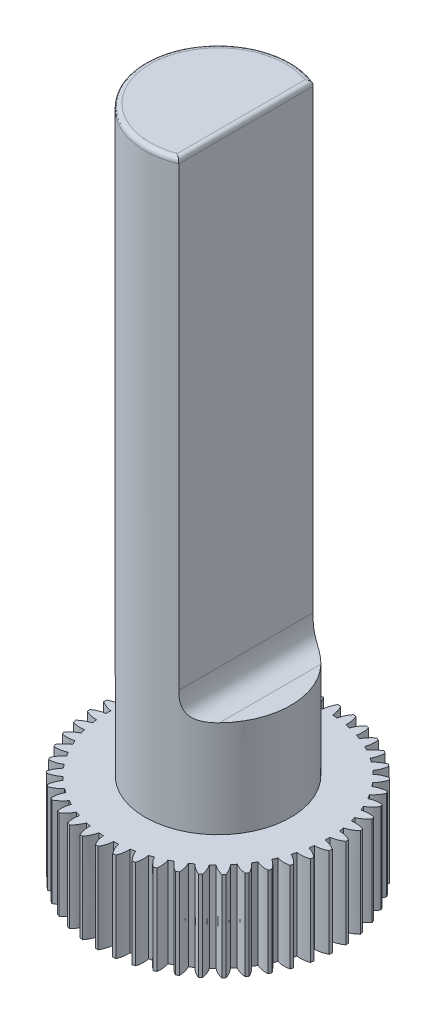
SolidWorks part; units mm, degrees
ref_plane "Front Plane" through (0, 0, 0) normal (0, 0, 1) x (1, 0, 0)
ref_plane "Top Plane" through (0, 0, 0) normal (0, 1, 0) x (1, 0, 0)
ref_plane "Right Plane" through (0, 0, 0) normal (1, 0, 0) x (0, 0, -1)
sketch "Sketch1" plane through (0, 0, 0) normal (0, 1, 0) x (1, 0, 0)
  circle A0 centre (0, 0) radius 1.5
  dimension "D1" = 3
extrude "Boss-Extrude1" add sketch "Sketch1" along normal blind 12
sketch "Sketch2" plane through (0, 12, 0) normal (0, 1, 0) x (1, 0, 0)
  line L0 (0.576, 1.385) -> (0.576, -1.385)
  circle A0 centre (0, 0) radius 1.5 construction
  arc A1 (0.576, -1.385) -> (0.576, 1.385) centre (0, 0) ccw
  dimension "D1" = 2.77
extrude "Cut-Extrude1" cut sketch "Sketch2" against normal blind 10
fillet "Fillet2" radius 0.5 1 edges at (0.576, 2, 0) curvature continuous yes
fillet "Fillet3" radius 0.1 2 edges at (-1.5, 12, 0) (0.576, 12, 0) curvature continuous yes
sketch "Sketch3" plane through (0, 0, 0) normal (0, -1, 0) x (1, 0, 0)
  circle A0 centre (0, 0) radius 2.26
  dimension "D1" = 4.52
extrude "Boss-Extrude2" add sketch "Sketch3" along normal blind 1.85
sketch "Sketch4" plane through (0, -1.85, 0) normal (0, -1, 0) x (1, 0, 0)
  line L0 (0, 3.4014) -> (0, -2.7756) construction
  line L1 (-0.03, 2.5) -> (0.03, 2.5)
  line L2 (0.3107, 2.4808) -> (0.3701, 2.4726)
  line L3 (0.105, 2.7453) -> (0.105, 2.2073) construction
  line L4 (0.6456, 2.4154) -> (0.7034, 2.3992)
  line L5 (0.9685, 2.305) -> (1.0235, 2.2811)
  line L6 (1.2733, 2.1516) -> (1.3246, 2.1205)
  line L7 (1.5544, 1.9582) -> (1.601, 1.9203)
  line L8 (1.8066, 1.7283) -> (1.8476, 1.6845)
  line L9 (2.0251, 1.4662) -> (2.0597, 1.4172)
  line L10 (2.2059, 1.1768) -> (2.2335, 1.1235)
  line L11 (2.3456, 0.8655) -> (2.3657, 0.8089)
  line L12 (2.4416, 0.538) -> (2.4538, 0.4793)
  line L13 (2.4921, 0.2005) -> (2.4962, 0.1407)
  line L14 (2.4962, -0.1407) -> (2.4921, -0.2005)
  line L15 (2.4538, -0.4793) -> (2.4416, -0.538)
  line L16 (2.3657, -0.8089) -> (2.3456, -0.8655)
  line L17 (2.2335, -1.1235) -> (2.2059, -1.1768)
  line L18 (2.0597, -1.4172) -> (2.0251, -1.4662)
  line L19 (1.8476, -1.6845) -> (1.8066, -1.7283)
  line L20 (1.601, -1.9203) -> (1.5544, -1.9582)
  line L21 (1.3246, -2.1205) -> (1.2733, -2.1516)
  line L22 (1.0235, -2.2811) -> (0.9685, -2.305)
  line L23 (0.7034, -2.3992) -> (0.6456, -2.4154)
  line L24 (0.3701, -2.4726) -> (0.3107, -2.4808)
  line L25 (0.03, -2.5) -> (-0.03, -2.5)
  line L26 (-0.3107, -2.4808) -> (-0.3701, -2.4726)
  line L27 (-0.6456, -2.4154) -> (-0.7034, -2.3992)
  line L28 (-0.9685, -2.305) -> (-1.0235, -2.2811)
  line L29 (-1.2733, -2.1516) -> (-1.3246, -2.1205)
  line L30 (-1.5544, -1.9582) -> (-1.601, -1.9203)
  line L31 (-1.8066, -1.7283) -> (-1.8476, -1.6845)
  line L32 (-2.0251, -1.4662) -> (-2.0597, -1.4172)
  line L33 (-2.2059, -1.1768) -> (-2.2335, -1.1235)
  line L34 (-2.3456, -0.8655) -> (-2.3657, -0.8089)
  line L35 (-2.4416, -0.538) -> (-2.4538, -0.4793)
  line L36 (-2.4921, -0.2005) -> (-2.4962, -0.1407)
  line L37 (-2.4962, 0.1407) -> (-2.4921, 0.2005)
  line L38 (-2.4538, 0.4793) -> (-2.4416, 0.538)
  line L39 (-2.3657, 0.8089) -> (-2.3456, 0.8655)
  line L40 (-2.2335, 1.1235) -> (-2.2059, 1.1768)
  line L41 (-2.0597, 1.4172) -> (-2.0251, 1.4662)
  line L42 (-1.8476, 1.6845) -> (-1.8066, 1.7283)
  line L43 (-1.601, 1.9203) -> (-1.5544, 1.9582)
  line L44 (-1.3246, 2.1205) -> (-1.2733, 2.1516)
  line L45 (-1.0235, 2.2811) -> (-0.9685, 2.305)
  line L46 (-0.7034, 2.3992) -> (-0.6456, 2.4154)
  line L47 (-0.3701, 2.4726) -> (-0.3107, 2.4808)
  circle A0 centre (0, 0) radius 2.26 construction
  spline S0 degree 2 poles (0.03, 2.5) (0.0998, 2.3793) (0.105, 2.2491) knots 0 0 0 0.862406 0.862406 0.862406
  spline S1 degree 1 poles (0, 2.26) (0.105, 2.2491) knots 0 0 1 1
  spline S2 degree 1 poles (0, 2.26) (-0.105, 2.2491) knots 0 0 1 1
  spline S3 degree 2 poles (-0.03, 2.5) (-0.0998, 2.3793) (-0.105, 2.2491) knots 0 0 0 0.862406 0.862406 0.862406
  spline S4 degree 2 poles (0.3107, 2.4808) (0.2251, 2.3707) (0.2022, 2.2424) knots 0 0 0 0.862406 0.862406 0.862406
  spline S5 degree 1 poles (0.3077, 2.239) (0.2022, 2.2424) knots 0 0 1 1
  spline S6 degree 1 poles (0.3077, 2.239) (0.4103, 2.2138) knots 0 0 1 1
  spline S7 degree 2 poles (0.3701, 2.4726) (0.4229, 2.3435) (0.4103, 2.2138) knots 0 0 0 0.862406 0.862406 0.862406
  spline S8 degree 2 poles (0.6456, 2.4154) (0.5458, 2.318) (0.5057, 2.194) knots 0 0 0 0.862406 0.862406 0.862406
  spline S9 degree 1 poles (0.6097, 2.1762) (0.5057, 2.194) knots 0 0 1 1
  spline S10 degree 1 poles (0.6097, 2.1762) (0.7079, 2.1373) knots 0 0 1 1
  spline S11 degree 2 poles (0.7034, 2.3992) (0.7381, 2.2641) (0.7079, 2.1373) knots 0 0 0 0.862406 0.862406 0.862406
  spline S12 degree 2 poles (0.9685, 2.305) (0.8563, 2.2221) (0.7997, 2.1047) knots 0 0 0 0.862406 0.862406 0.862406
  spline S13 degree 1 poles (0.9004, 2.0729) (0.7997, 2.1047) knots 0 0 1 1
  spline S14 degree 1 poles (0.9004, 2.0729) (0.9923, 2.021) knots 0 0 1 1
  spline S15 degree 2 poles (1.0235, 2.2811) (1.0395, 2.1425) (0.9923, 2.021) knots 0 0 0 0.862406 0.862406 0.862406
  spline S16 degree 2 poles (1.2733, 2.1516) (1.1509, 2.0848) (1.0789, 1.9762) knots 0 0 0 0.862406 0.862406 0.862406
  spline S17 degree 1 poles (1.1743, 1.931) (1.0789, 1.9762) knots 0 0 1 1
  spline S18 degree 1 poles (1.1743, 1.931) (1.2583, 1.8671) knots 0 0 1 1
  spline S19 degree 2 poles (1.3246, 2.1205) (1.3215, 1.981) (1.2583, 1.8671) knots 0 0 0 0.862406 0.862406 0.862406
  spline S20 degree 2 poles (1.5544, 1.9582) (1.4241, 1.9086) (1.3379, 1.8109) knots 0 0 0 0.862406 0.862406 0.862406
  spline S21 degree 1 poles (1.4263, 1.7531) (1.3379, 1.8109) knots 0 0 1 1
  spline S22 degree 1 poles (1.4263, 1.7531) (1.5008, 1.6784) knots 0 0 1 1
  spline S23 degree 2 poles (1.601, 1.9203) (1.579, 1.7826) (1.5008, 1.6784) knots 0 0 0 0.862406 0.862406 0.862406
  spline S24 degree 2 poles (1.8066, 1.7283) (1.6707, 1.6969) (1.572, 1.6118) knots 0 0 0 0.862406 0.862406 0.862406
  spline S25 degree 1 poles (1.6517, 1.5426) (1.572, 1.6118) knots 0 0 1 1
  spline S26 degree 1 poles (1.6517, 1.5426) (1.7154, 1.4584) knots 0 0 1 1
  spline S27 degree 2 poles (1.8476, 1.6845) (1.807, 1.551) (1.7154, 1.4584) knots 0 0 0 0.862406 0.862406 0.862406
  spline S28 degree 2 poles (2.0251, 1.4662) (1.8862, 1.4536) (1.7769, 1.3828) knots 0 0 0 0.862406 0.862406 0.862406
  spline S29 degree 1 poles (1.8464, 1.3033) (1.7769, 1.3828) knots 0 0 1 1
  spline S30 degree 1 poles (1.8464, 1.3033) (1.898, 1.2112) knots 0 0 1 1
  spline S31 degree 2 poles (2.0597, 1.4172) (2.0014, 1.2905) (1.898, 1.2112) knots 0 0 0 0.862406 0.862406 0.862406
  spline S32 degree 2 poles (2.2059, 1.1768) (2.0666, 1.1833) (1.9486, 1.1279) knots 0 0 0 0.862406 0.862406 0.862406
  spline S33 degree 1 poles (2.0066, 1.0397) (1.9486, 1.1279) knots 0 0 1 1
  spline S34 degree 1 poles (2.0066, 1.0397) (2.0452, 0.9415) knots 0 0 1 1
  spline S35 degree 2 poles (2.2335, 1.1235) (2.1584, 1.006) (2.0452, 0.9415) knots 0 0 0 0.862406 0.862406 0.862406
  spline S36 degree 2 poles (2.3456, 0.8655) (2.2085, 0.8908) (2.084, 0.8521) knots 0 0 0 0.862406 0.862406 0.862406
  spline S37 degree 1 poles (2.1295, 0.7568) (2.084, 0.8521) knots 0 0 1 1
  spline S38 degree 1 poles (2.1295, 0.7568) (2.1544, 0.6542) knots 0 0 1 1
  spline S39 degree 2 poles (2.3657, 0.8089) (2.2753, 0.7027) (2.1544, 0.6542) knots 0 0 0 0.862406 0.862406 0.862406
  spline S40 degree 2 poles (2.4416, 0.538) (2.3092, 0.5818) (2.1807, 0.5604) knots 0 0 0 0.862406 0.862406 0.862406
  spline S41 degree 1 poles (2.2127, 0.4598) (2.1807, 0.5604) knots 0 0 1 1
  spline S42 degree 1 poles (2.2127, 0.4598) (2.2234, 0.3548) knots 0 0 1 1
  spline S43 degree 2 poles (2.4538, 0.4793) (2.3498, 0.3863) (2.2234, 0.3548) knots 0 0 0 0.862406 0.862406 0.862406
  spline S44 degree 2 poles (2.4921, 0.2005) (2.3669, 0.262) (2.2367, 0.2582) knots 0 0 0 0.862406 0.862406 0.862406
  spline S45 degree 1 poles (2.2547, 0.1542) (2.2367, 0.2582) knots 0 0 1 1
  spline S46 degree 1 poles (2.2547, 0.1542) (2.251, 0.0487) knots 0 0 1 1
  spline S47 degree 2 poles (2.4962, 0.1407) (2.3805, 0.0628) (2.251, 0.0487) knots 0 0 0 0.862406 0.862406 0.862406
  spline S48 degree 2 poles (2.4962, -0.1407) (2.3805, -0.0628) (2.251, -0.0487) knots 0 0 0 0.862406 0.862406 0.862406
  spline S49 degree 1 poles (2.2547, -0.1542) (2.251, -0.0487) knots 0 0 1 1
  spline S50 degree 1 poles (2.2547, -0.1542) (2.2367, -0.2582) knots 0 0 1 1
  spline S51 degree 2 poles (2.4921, -0.2005) (2.3669, -0.262) (2.2367, -0.2582) knots 0 0 0 0.862406 0.862406 0.862406
  spline S52 degree 2 poles (2.4538, -0.4793) (2.3498, -0.3863) (2.2234, -0.3548) knots 0 0 0 0.862406 0.862406 0.862406
  spline S53 degree 1 poles (2.2127, -0.4598) (2.2234, -0.3548) knots 0 0 1 1
  spline S54 degree 1 poles (2.2127, -0.4598) (2.1807, -0.5604) knots 0 0 1 1
  spline S55 degree 2 poles (2.4416, -0.538) (2.3092, -0.5818) (2.1807, -0.5604) knots 0 0 0 0.862406 0.862406 0.862406
  spline S56 degree 2 poles (2.3657, -0.8089) (2.2753, -0.7027) (2.1544, -0.6542) knots 0 0 0 0.862406 0.862406 0.862406
  spline S57 degree 1 poles (2.1295, -0.7568) (2.1544, -0.6542) knots 0 0 1 1
  spline S58 degree 1 poles (2.1295, -0.7568) (2.084, -0.8521) knots 0 0 1 1
  spline S59 degree 2 poles (2.3456, -0.8655) (2.2085, -0.8908) (2.084, -0.8521) knots 0 0 0 0.862406 0.862406 0.862406
  spline S60 degree 2 poles (2.2335, -1.1235) (2.1584, -1.006) (2.0452, -0.9415) knots 0 0 0 0.862406 0.862406 0.862406
  spline S61 degree 1 poles (2.0066, -1.0397) (2.0452, -0.9415) knots 0 0 1 1
  spline S62 degree 1 poles (2.0066, -1.0397) (1.9486, -1.1279) knots 0 0 1 1
  spline S63 degree 2 poles (2.2059, -1.1768) (2.0666, -1.1833) (1.9486, -1.1279) knots 0 0 0 0.862406 0.862406 0.862406
  spline S64 degree 2 poles (2.0597, -1.4172) (2.0014, -1.2905) (1.898, -1.2112) knots 0 0 0 0.862406 0.862406 0.862406
  spline S65 degree 1 poles (1.8464, -1.3033) (1.898, -1.2112) knots 0 0 1 1
  spline S66 degree 1 poles (1.8464, -1.3033) (1.7769, -1.3828) knots 0 0 1 1
  spline S67 degree 2 poles (2.0251, -1.4662) (1.8862, -1.4536) (1.7769, -1.3828) knots 0 0 0 0.862406 0.862406 0.862406
  spline S68 degree 2 poles (1.8476, -1.6845) (1.807, -1.551) (1.7154, -1.4584) knots 0 0 0 0.862406 0.862406 0.862406
  spline S69 degree 1 poles (1.6517, -1.5426) (1.7154, -1.4584) knots 0 0 1 1
  spline S70 degree 1 poles (1.6517, -1.5426) (1.572, -1.6118) knots 0 0 1 1
  spline S71 degree 2 poles (1.8066, -1.7283) (1.6707, -1.6969) (1.572, -1.6118) knots 0 0 0 0.862406 0.862406 0.862406
  spline S72 degree 2 poles (1.601, -1.9203) (1.579, -1.7826) (1.5008, -1.6784) knots 0 0 0 0.862406 0.862406 0.862406
  spline S73 degree 1 poles (1.4263, -1.7531) (1.5008, -1.6784) knots 0 0 1 1
  spline S74 degree 1 poles (1.4263, -1.7531) (1.3379, -1.8109) knots 0 0 1 1
  spline S75 degree 2 poles (1.5544, -1.9582) (1.4241, -1.9086) (1.3379, -1.8109) knots 0 0 0 0.862406 0.862406 0.862406
  spline S76 degree 2 poles (1.3246, -2.1205) (1.3215, -1.981) (1.2583, -1.8671) knots 0 0 0 0.862406 0.862406 0.862406
  spline S77 degree 1 poles (1.1743, -1.931) (1.2583, -1.8671) knots 0 0 1 1
  spline S78 degree 1 poles (1.1743, -1.931) (1.0789, -1.9762) knots 0 0 1 1
  spline S79 degree 2 poles (1.2733, -2.1516) (1.1509, -2.0848) (1.0789, -1.9762) knots 0 0 0 0.862406 0.862406 0.862406
  spline S80 degree 2 poles (1.0235, -2.2811) (1.0395, -2.1425) (0.9923, -2.021) knots 0 0 0 0.862406 0.862406 0.862406
  spline S81 degree 1 poles (0.9004, -2.0729) (0.9923, -2.021) knots 0 0 1 1
  spline S82 degree 1 poles (0.9004, -2.0729) (0.7997, -2.1047) knots 0 0 1 1
  spline S83 degree 2 poles (0.9685, -2.305) (0.8563, -2.2221) (0.7997, -2.1047) knots 0 0 0 0.862406 0.862406 0.862406
  spline S84 degree 2 poles (0.7034, -2.3992) (0.7381, -2.2641) (0.7079, -2.1373) knots 0 0 0 0.862406 0.862406 0.862406
  spline S85 degree 1 poles (0.6097, -2.1762) (0.7079, -2.1373) knots 0 0 1 1
  spline S86 degree 1 poles (0.6097, -2.1762) (0.5057, -2.194) knots 0 0 1 1
  spline S87 degree 2 poles (0.6456, -2.4154) (0.5458, -2.318) (0.5057, -2.194) knots 0 0 0 0.862406 0.862406 0.862406
  spline S88 degree 2 poles (0.3701, -2.4726) (0.4229, -2.3435) (0.4103, -2.2138) knots 0 0 0 0.862406 0.862406 0.862406
  spline S89 degree 1 poles (0.3077, -2.239) (0.4103, -2.2138) knots 0 0 1 1
  spline S90 degree 1 poles (0.3077, -2.239) (0.2022, -2.2424) knots 0 0 1 1
  spline S91 degree 2 poles (0.3107, -2.4808) (0.2251, -2.3707) (0.2022, -2.2424) knots 0 0 0 0.862406 0.862406 0.862406
  spline S92 degree 2 poles (0.03, -2.5) (0.0998, -2.3793) (0.105, -2.2491) knots 0 0 0 0.862406 0.862406 0.862406
  spline S93 degree 1 poles (0, -2.26) (0.105, -2.2491) knots 0 0 1 1
  spline S94 degree 1 poles (0, -2.26) (-0.105, -2.2491) knots 0 0 1 1
  spline S95 degree 2 poles (-0.03, -2.5) (-0.0998, -2.3793) (-0.105, -2.2491) knots 0 0 0 0.862406 0.862406 0.862406
  spline S96 degree 2 poles (-0.3107, -2.4808) (-0.2251, -2.3707) (-0.2022, -2.2424) knots 0 0 0 0.862406 0.862406 0.862406
  spline S97 degree 1 poles (-0.3077, -2.239) (-0.2022, -2.2424) knots 0 0 1 1
  spline S98 degree 1 poles (-0.3077, -2.239) (-0.4103, -2.2138) knots 0 0 1 1
  spline S99 degree 2 poles (-0.3701, -2.4726) (-0.4229, -2.3435) (-0.4103, -2.2138) knots 0 0 0 0.862406 0.862406 0.862406
  spline S100 degree 2 poles (-0.6456, -2.4154) (-0.5458, -2.318) (-0.5057, -2.194) knots 0 0 0 0.862406 0.862406 0.862406
  spline S101 degree 1 poles (-0.6097, -2.1762) (-0.5057, -2.194) knots 0 0 1 1
  spline S102 degree 1 poles (-0.6097, -2.1762) (-0.7079, -2.1373) knots 0 0 1 1
  spline S103 degree 2 poles (-0.7034, -2.3992) (-0.7381, -2.2641) (-0.7079, -2.1373) knots 0 0 0 0.862406 0.862406 0.862406
  spline S104 degree 2 poles (-0.9685, -2.305) (-0.8563, -2.2221) (-0.7997, -2.1047) knots 0 0 0 0.862406 0.862406 0.862406
  spline S105 degree 1 poles (-0.9004, -2.0729) (-0.7997, -2.1047) knots 0 0 1 1
  spline S106 degree 1 poles (-0.9004, -2.0729) (-0.9923, -2.021) knots 0 0 1 1
  spline S107 degree 2 poles (-1.0235, -2.2811) (-1.0395, -2.1425) (-0.9923, -2.021) knots 0 0 0 0.862406 0.862406 0.862406
  spline S108 degree 2 poles (-1.2733, -2.1516) (-1.1509, -2.0848) (-1.0789, -1.9762) knots 0 0 0 0.862406 0.862406 0.862406
  spline S109 degree 1 poles (-1.1743, -1.931) (-1.0789, -1.9762) knots 0 0 1 1
  spline S110 degree 1 poles (-1.1743, -1.931) (-1.2583, -1.8671) knots 0 0 1 1
  spline S111 degree 2 poles (-1.3246, -2.1205) (-1.3215, -1.981) (-1.2583, -1.8671) knots 0 0 0 0.862406 0.862406 0.862406
  spline S112 degree 2 poles (-1.5544, -1.9582) (-1.4241, -1.9086) (-1.3379, -1.8109) knots 0 0 0 0.862406 0.862406 0.862406
  spline S113 degree 1 poles (-1.4263, -1.7531) (-1.3379, -1.8109) knots 0 0 1 1
  spline S114 degree 1 poles (-1.4263, -1.7531) (-1.5008, -1.6784) knots 0 0 1 1
  spline S115 degree 2 poles (-1.601, -1.9203) (-1.579, -1.7826) (-1.5008, -1.6784) knots 0 0 0 0.862406 0.862406 0.862406
  spline S116 degree 2 poles (-1.8066, -1.7283) (-1.6707, -1.6969) (-1.572, -1.6118) knots 0 0 0 0.862406 0.862406 0.862406
  spline S117 degree 1 poles (-1.6517, -1.5426) (-1.572, -1.6118) knots 0 0 1 1
  spline S118 degree 1 poles (-1.6517, -1.5426) (-1.7154, -1.4584) knots 0 0 1 1
  spline S119 degree 2 poles (-1.8476, -1.6845) (-1.807, -1.551) (-1.7154, -1.4584) knots 0 0 0 0.862406 0.862406 0.862406
  spline S120 degree 2 poles (-2.0251, -1.4662) (-1.8862, -1.4536) (-1.7769, -1.3828) knots 0 0 0 0.862406 0.862406 0.862406
  spline S121 degree 1 poles (-1.8464, -1.3033) (-1.7769, -1.3828) knots 0 0 1 1
  spline S122 degree 1 poles (-1.8464, -1.3033) (-1.898, -1.2112) knots 0 0 1 1
  spline S123 degree 2 poles (-2.0597, -1.4172) (-2.0014, -1.2905) (-1.898, -1.2112) knots 0 0 0 0.862406 0.862406 0.862406
  spline S124 degree 2 poles (-2.2059, -1.1768) (-2.0666, -1.1833) (-1.9486, -1.1279) knots 0 0 0 0.862406 0.862406 0.862406
  spline S125 degree 1 poles (-2.0066, -1.0397) (-1.9486, -1.1279) knots 0 0 1 1
  spline S126 degree 1 poles (-2.0066, -1.0397) (-2.0452, -0.9415) knots 0 0 1 1
  spline S127 degree 2 poles (-2.2335, -1.1235) (-2.1584, -1.006) (-2.0452, -0.9415) knots 0 0 0 0.862406 0.862406 0.862406
  spline S128 degree 2 poles (-2.3456, -0.8655) (-2.2085, -0.8908) (-2.084, -0.8521) knots 0 0 0 0.862406 0.862406 0.862406
  spline S129 degree 1 poles (-2.1295, -0.7568) (-2.084, -0.8521) knots 0 0 1 1
  spline S130 degree 1 poles (-2.1295, -0.7568) (-2.1544, -0.6542) knots 0 0 1 1
  spline S131 degree 2 poles (-2.3657, -0.8089) (-2.2753, -0.7027) (-2.1544, -0.6542) knots 0 0 0 0.862406 0.862406 0.862406
  spline S132 degree 2 poles (-2.4416, -0.538) (-2.3092, -0.5818) (-2.1807, -0.5604) knots 0 0 0 0.862406 0.862406 0.862406
  spline S133 degree 1 poles (-2.2127, -0.4598) (-2.1807, -0.5604) knots 0 0 1 1
  spline S134 degree 1 poles (-2.2127, -0.4598) (-2.2234, -0.3548) knots 0 0 1 1
  spline S135 degree 2 poles (-2.4538, -0.4793) (-2.3498, -0.3863) (-2.2234, -0.3548) knots 0 0 0 0.862406 0.862406 0.862406
  spline S136 degree 2 poles (-2.4921, -0.2005) (-2.3669, -0.262) (-2.2367, -0.2582) knots 0 0 0 0.862406 0.862406 0.862406
  spline S137 degree 1 poles (-2.2547, -0.1542) (-2.2367, -0.2582) knots 0 0 1 1
  spline S138 degree 1 poles (-2.2547, -0.1542) (-2.251, -0.0487) knots 0 0 1 1
  spline S139 degree 2 poles (-2.4962, -0.1407) (-2.3805, -0.0628) (-2.251, -0.0487) knots 0 0 0 0.862406 0.862406 0.862406
  spline S140 degree 2 poles (-2.4962, 0.1407) (-2.3805, 0.0628) (-2.251, 0.0487) knots 0 0 0 0.862406 0.862406 0.862406
  spline S141 degree 1 poles (-2.2547, 0.1542) (-2.251, 0.0487) knots 0 0 1 1
  spline S142 degree 1 poles (-2.2547, 0.1542) (-2.2367, 0.2582) knots 0 0 1 1
  spline S143 degree 2 poles (-2.4921, 0.2005) (-2.3669, 0.262) (-2.2367, 0.2582) knots 0 0 0 0.862406 0.862406 0.862406
  spline S144 degree 2 poles (-2.4538, 0.4793) (-2.3498, 0.3863) (-2.2234, 0.3548) knots 0 0 0 0.862406 0.862406 0.862406
  spline S145 degree 1 poles (-2.2127, 0.4598) (-2.2234, 0.3548) knots 0 0 1 1
  spline S146 degree 1 poles (-2.2127, 0.4598) (-2.1807, 0.5604) knots 0 0 1 1
  spline S147 degree 2 poles (-2.4416, 0.538) (-2.3092, 0.5818) (-2.1807, 0.5604) knots 0 0 0 0.862406 0.862406 0.862406
  spline S148 degree 2 poles (-2.3657, 0.8089) (-2.2753, 0.7027) (-2.1544, 0.6542) knots 0 0 0 0.862406 0.862406 0.862406
  spline S149 degree 1 poles (-2.1295, 0.7568) (-2.1544, 0.6542) knots 0 0 1 1
  spline S150 degree 1 poles (-2.1295, 0.7568) (-2.084, 0.8521) knots 0 0 1 1
  spline S151 degree 2 poles (-2.3456, 0.8655) (-2.2085, 0.8908) (-2.084, 0.8521) knots 0 0 0 0.862406 0.862406 0.862406
  spline S152 degree 2 poles (-2.2335, 1.1235) (-2.1584, 1.006) (-2.0452, 0.9415) knots 0 0 0 0.862406 0.862406 0.862406
  spline S153 degree 1 poles (-2.0066, 1.0397) (-2.0452, 0.9415) knots 0 0 1 1
  spline S154 degree 1 poles (-2.0066, 1.0397) (-1.9486, 1.1279) knots 0 0 1 1
  spline S155 degree 2 poles (-2.2059, 1.1768) (-2.0666, 1.1833) (-1.9486, 1.1279) knots 0 0 0 0.862406 0.862406 0.862406
  spline S156 degree 2 poles (-2.0597, 1.4172) (-2.0014, 1.2905) (-1.898, 1.2112) knots 0 0 0 0.862406 0.862406 0.862406
  spline S157 degree 1 poles (-1.8464, 1.3033) (-1.898, 1.2112) knots 0 0 1 1
  spline S158 degree 1 poles (-1.8464, 1.3033) (-1.7769, 1.3828) knots 0 0 1 1
  spline S159 degree 2 poles (-2.0251, 1.4662) (-1.8862, 1.4536) (-1.7769, 1.3828) knots 0 0 0 0.862406 0.862406 0.862406
  spline S160 degree 2 poles (-1.8476, 1.6845) (-1.807, 1.551) (-1.7154, 1.4584) knots 0 0 0 0.862406 0.862406 0.862406
  spline S161 degree 1 poles (-1.6517, 1.5426) (-1.7154, 1.4584) knots 0 0 1 1
  spline S162 degree 1 poles (-1.6517, 1.5426) (-1.572, 1.6118) knots 0 0 1 1
  spline S163 degree 2 poles (-1.8066, 1.7283) (-1.6707, 1.6969) (-1.572, 1.6118) knots 0 0 0 0.862406 0.862406 0.862406
  spline S164 degree 2 poles (-1.601, 1.9203) (-1.579, 1.7826) (-1.5008, 1.6784) knots 0 0 0 0.862406 0.862406 0.862406
  spline S165 degree 1 poles (-1.4263, 1.7531) (-1.5008, 1.6784) knots 0 0 1 1
  spline S166 degree 1 poles (-1.4263, 1.7531) (-1.3379, 1.8109) knots 0 0 1 1
  spline S167 degree 2 poles (-1.5544, 1.9582) (-1.4241, 1.9086) (-1.3379, 1.8109) knots 0 0 0 0.862406 0.862406 0.862406
  spline S168 degree 2 poles (-1.3246, 2.1205) (-1.3215, 1.981) (-1.2583, 1.8671) knots 0 0 0 0.862406 0.862406 0.862406
  spline S169 degree 1 poles (-1.1743, 1.931) (-1.2583, 1.8671) knots 0 0 1 1
  spline S170 degree 1 poles (-1.1743, 1.931) (-1.0789, 1.9762) knots 0 0 1 1
  spline S171 degree 2 poles (-1.2733, 2.1516) (-1.1509, 2.0848) (-1.0789, 1.9762) knots 0 0 0 0.862406 0.862406 0.862406
  spline S172 degree 2 poles (-1.0235, 2.2811) (-1.0395, 2.1425) (-0.9923, 2.021) knots 0 0 0 0.862406 0.862406 0.862406
  spline S173 degree 1 poles (-0.9004, 2.0729) (-0.9923, 2.021) knots 0 0 1 1
  spline S174 degree 1 poles (-0.9004, 2.0729) (-0.7997, 2.1047) knots 0 0 1 1
  spline S175 degree 2 poles (-0.9685, 2.305) (-0.8563, 2.2221) (-0.7997, 2.1047) knots 0 0 0 0.862406 0.862406 0.862406
  spline S176 degree 2 poles (-0.7034, 2.3992) (-0.7381, 2.2641) (-0.7079, 2.1373) knots 0 0 0 0.862406 0.862406 0.862406
  spline S177 degree 1 poles (-0.6097, 2.1762) (-0.7079, 2.1373) knots 0 0 1 1
  spline S178 degree 1 poles (-0.6097, 2.1762) (-0.5057, 2.194) knots 0 0 1 1
  spline S179 degree 2 poles (-0.6456, 2.4154) (-0.5458, 2.318) (-0.5057, 2.194) knots 0 0 0 0.862406 0.862406 0.862406
  spline S180 degree 2 poles (-0.3701, 2.4726) (-0.4229, 2.3435) (-0.4103, 2.2138) knots 0 0 0 0.862406 0.862406 0.862406
  spline S181 degree 1 poles (-0.3077, 2.239) (-0.4103, 2.2138) knots 0 0 1 1
  spline S182 degree 1 poles (-0.3077, 2.239) (-0.2022, 2.2424) knots 0 0 1 1
  spline S183 degree 2 poles (-0.3107, 2.4808) (-0.2251, 2.3707) (-0.2022, 2.2424) knots 0 0 0 0.862406 0.862406 0.862406
  point P13 (0, 2.5)
  dimension "D1" = 0.03
  dimension "D2" = 0.105
  dimension "D3" = 2.5
  dimension "D4" = 46
extrude "Boss-Extrude3" add sketch "Sketch4" against normal blind 1.85
sketch "Sketch5" plane through (0, -1.85, 0) normal (0, -1, 0) x (1, 0, 0)
  circle A0 centre (0, 0) radius 0.5
  dimension "D1" = 1
extrude "Cut-Extrude2" cut sketch "Sketch5" against normal blind 1
